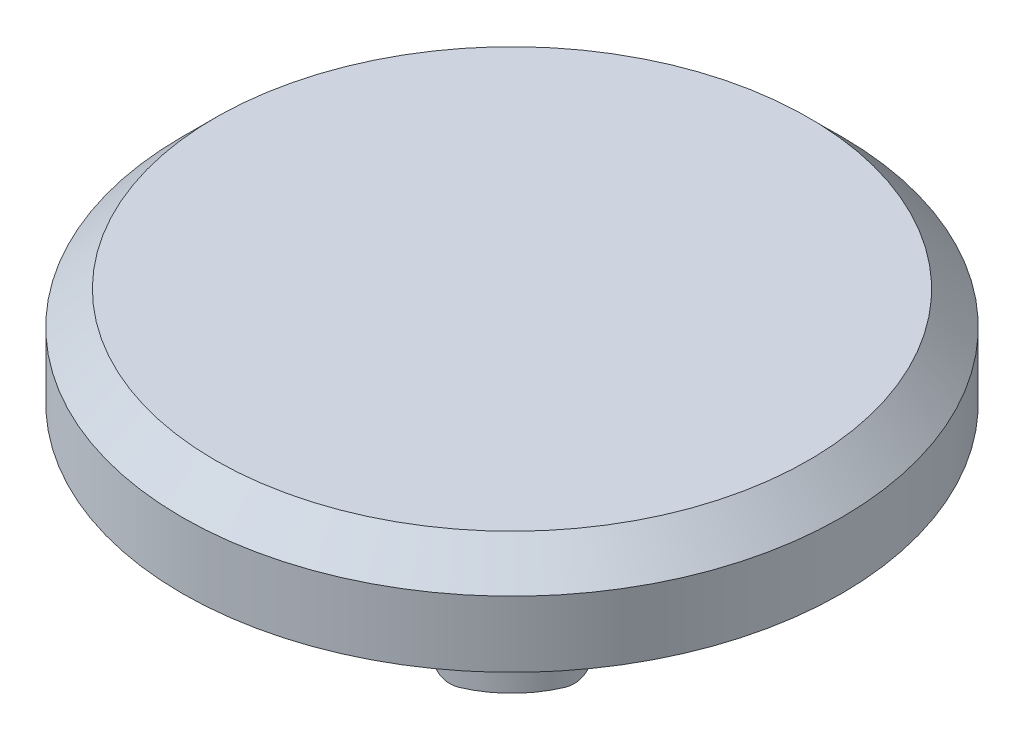
SolidWorks part; units mm, degrees
ref_plane "Front Plane" through (0, 0, 0) normal (0, 0, 1) x (1, 0, 0)
ref_plane "Top Plane" through (0, 0, 0) normal (0, 1, 0) x (1, 0, 0)
ref_plane "Right Plane" through (0, 0, 0) normal (1, 0, 0) x (0, 0, -1)
sketch "Sketch1" plane through (0, 0, 0) normal (0, 1, 0) x (1, 0, 0)
  circle A0 centre (0, 0) radius 10
  dimension "D1" = 20
extrude "Boss-Extrude1" add sketch "Sketch1" along normal blind 3
sketch "Sketch2" plane through (0, 0, 0) normal (0, -1, 0) x (1, 0, 0)
  circle A0 centre (0, 0) radius 3
  dimension "D1" = 6
extrude "Boss-Extrude2" add sketch "Sketch2" along normal blind 5.5
sketch "Sketch3" plane through (0, -5.5, 0) normal (0, -1, 0) x (1, 0, 0)
  line L0 (0.55, 0.55) -> (5.5362, 0.55)
  line L1 (-5.5362, 0.55) -> (-0.65, 0.55)
  line L2 (-5.5362, 0.55) -> (-5.5362, -0.65)
  line L3 (-5.5362, -0.65) -> (-0.65, -0.65)
  line L4 (5.5362, 0.55) -> (5.5362, -0.65)
  line L7 (-0.65, 5.1643) -> (0.55, 5.1643)
  line L8 (-0.65, 5.1643) -> (-0.65, 0.55)
  line L9 (-0.65, -5.1643) -> (0.55, -5.1643)
  line L10 (0.55, 5.1643) -> (0.55, 0.55)
  line L17 (0.55, -0.65) -> (5.5362, -0.65)
  line L18 (-0.65, -0.65) -> (-0.65, -5.1643)
  line L19 (0.55, -0.65) -> (0.55, -5.1643)
  point P0 (0, 0)
  point P6 (0, 0)
  dimension "D1" = 1.2
  dimension "D2" = 1.2
extrude "Cut-Extrude1" cut sketch "Sketch3" against normal blind 4.5
sketch "Sketch4" plane through (0, 0, 0) normal (0, -1, 0) x (1, 0, 0)
  text T0 "<b>Ct</b>" font "Century Gothic" height in points 14
extrude "Cut-Extrude2" cut sketch "Sketch4" against normal blind 2
fillet "Fillet3" radius 0.6 8 edges at (-0.65, -5.5, -1.7894) (0.55, -5.5, -1.7996) (-1.7894, -5.5, -0.65) (1.7394, -5.5, -0.65) (-1.7996, -5.5, 0.55) (1.7496, -5.5, 0.55) (0.55, -5.5, 1.7496) (-0.65, -5.5, 1.7394)
chamfer "Chamfer1" distance 1 angle 45 1 edges at (0, 3, 10)
fillet "Fillet4" radius 0.8 1 edges at (0, 0, 3)
